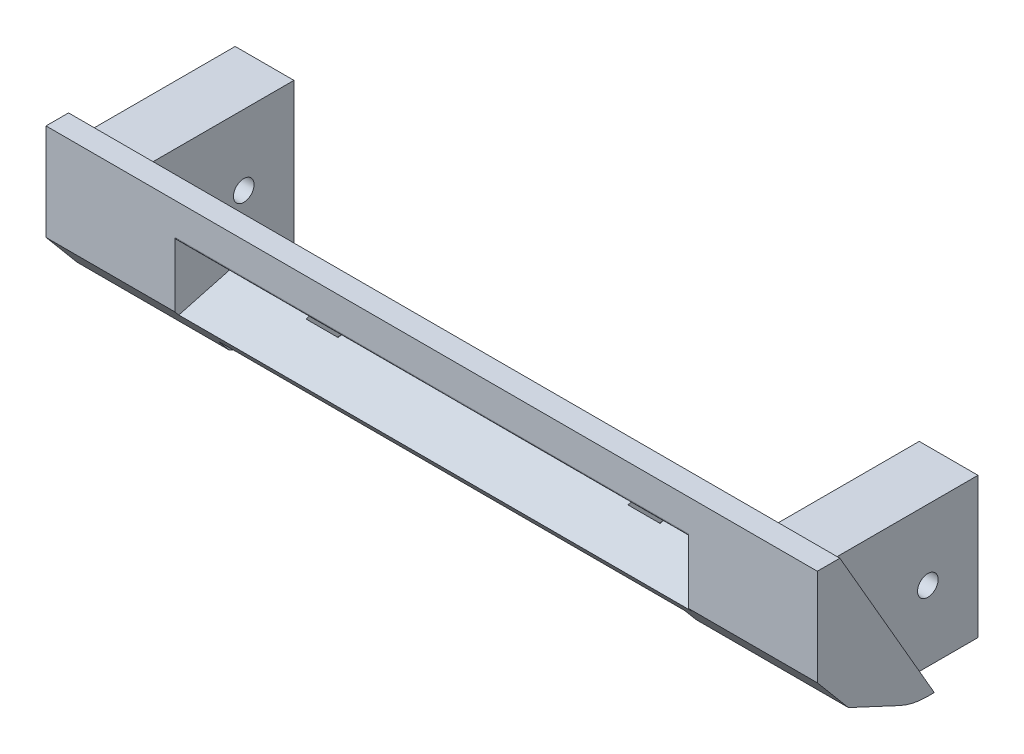
SolidWorks part; units mm, degrees
ref_plane "Front Plane" through (0, 0, 0) normal (0, 0, 1) x (1, 0, 0)
ref_plane "Top Plane" through (0, 0, 0) normal (0, 1, 0) x (1, 0, 0)
ref_plane "Right Plane" through (0, 0, 0) normal (1, 0, 0) x (0, 0, -1)
sketch "Sketch1" plane through (0, 0, 0) normal (1, 0, 0) x (0, 0, -1)
  line L0 (0, 0) -> (-29.3294, 50.8)
  line L1 (0, 0) -> (50, 0) construction
  line L2 (-29.3294, 50.8) -> (-36.3294, 50.8)
  line L3 (-36.3294, 13.8) -> (-6.7352, 0)
  line L6 (-36.3294, 50.8) -> (-36.3294, 13.8)
  line L7 (-6.7352, 0) -> (0, 0)
  line L8 (0, 0) -> (0, 21.8413) construction
  dimension "D1" = 65
  dimension "D2" = 6.7352
  dimension "D3" = 37
extrude "Boss-Extrude2" add sketch "Sketch1" along normal mid plane 239.55
sketch "Sketch2" plane through (0, 0, 0) normal (0, 0, 1) x (1, 0, 0)
  line L0 (0, 0) -> (0, 50.8) construction
  line L5 (115.75, 47.625) -> (96.7, 47.625) construction
  line L6 (115.75, 47.625) -> (115.75, 3.175) construction
  line L11 (115.75, 3.175) -> (96.7, 3.175) construction
  line L12 (96.7, 47.625) -> (96.7, 3.175) construction
  line L14 (115.35, 47.225) -> (115.35, 3.575)
  line L15 (115.35, 3.575) -> (97.1, 3.575)
  line L21 (119.775, 0) -> (-119.6, 0) construction
  line L28 (97.1, 47.225) -> (97.1, 3.575)
  line L29 (115.35, 47.225) -> (97.1, 47.225)
  line L30 (-96.7, 47.625) -> (-96.7, 3.175) construction
  line L31 (-115.75, 3.175) -> (-96.7, 3.175) construction
  line L32 (-115.75, 47.625) -> (-115.75, 3.175) construction
  line L33 (-115.75, 47.625) -> (-96.7, 47.625) construction
  line L34 (-115.35, 47.225) -> (-97.1, 47.225)
  line L35 (-97.1, 47.225) -> (-97.1, 3.575)
  line L36 (-115.35, 3.575) -> (-97.1, 3.575)
  line L37 (-115.35, 47.225) -> (-115.35, 3.575)
  line L40 (119.775, 50.8) -> (-119.775, 50.8) construction
  line L41 (119.775, 0) -> (119.775, 50.8) construction
  dimension "D2" = 19.05
  dimension "D4" = 3.175
  dimension "D7" = 4.025
  dimension "D1" = 193.4
  dimension "D3" = 3.175
  dimension "D5" = 0.4
extrude "Boss-Extrude1" add sketch "Sketch2" along normal up to surface and the other way blind 18 up to face at (0, 25.4, 14.6647)
sketch "Sketch12" plane through (0, -2.5797, 1.2029) normal (0, -0.9063, 0.4226) x (1, 0, 0)
  line L0 (-95.2, -603.0139) -> (-95.2, 0.9459) construction
  line L1 (-95.2, -603.0139) -> (-95.2, 0.9459) construction
  line L2 (119.775, 0) -> (-119.775, 0) construction
  line L3 (70, 15) -> (-70, 15)
  line L4 (70, 15) -> (70, 0)
  line L5 (70, 0) -> (-70, 0)
  line L6 (-70, 15) -> (-70, 0)
  line L7 (70, 15) -> (-70, 0) construction
  line L8 (70, 0) -> (-70, 15) construction
  line L10 (95.2, 44.3946) -> (-95.2, 44.3946)
  line L11 (95.2, 44.3946) -> (95.2, 19.3946)
  line L12 (95.2, 19.3946) -> (-95.2, 19.3946)
  line L13 (-95.2, 44.3946) -> (-95.2, 19.3946)
  line L14 (95.2, 44.3946) -> (-95.2, 19.3946) construction
  line L15 (95.2, 19.3946) -> (-95.2, 44.3946) construction
  line L16 (-120.6, 54.3946) -> (120.6, 54.3946) construction
  point P2 (0, 7.5)
  point P11 (0, 31.8946)
  dimension "D1" = 15
  dimension "D2" = 140
  dimension "D3" = 10
  dimension "D4" = 25
  dimension "D5" = 4.3946
extrude "Cut-Extrude4" [suppressed] cut sketch "Sketch12" against normal up to next
hole_wizard "M6 Clearance Hole1" positions "Sketch11" profile "Sketch10" hole size "M6" standard "ANSI Metric" end condition through all
sketch "Sketch11" plane through (115.35, 0, 0) normal (1, 0, 0) x (0, 0, -1)
  point P0 (2.4206, 25.4)
sketch "Sketch10" plane through (115.35, 25.4, -2.4206) normal (0, 1, 0) x (0, 0, -1)
  line L0 (0, 0) -> (0, 235.125)
  line L1 (0, 235.125) -> (3.2, 235.125)
  line L2 (3.2, 235.125) -> (3.2, 0)
  line L5 (3.2, 0) -> (0, 0)
  line L11 (0, -6.35) -> (0, 107.95) construction
  dimension "Thru Hole Dia." = 6.4
  dimension "Thru Hole Depth" = 235.125
sketch "Sketch13" plane through (0, 0, 0) normal (0, 0, 1) x (1, 0, 0)
  line L0 (119.775, 0) -> (-119.775, 0) construction
  line L1 (-72.5, 13.5) -> (72.5, 13.5)
  line L2 (-72.5, 13.5) -> (-72.5, 0)
  line L3 (-72.5, 0) -> (72.5, 0)
  line L4 (72.5, 13.5) -> (72.5, 0)
  line L5 (-72.5, 13.5) -> (72.5, 0) construction
  line L6 (-72.5, 0) -> (72.5, 13.5) construction
  line L7 (119.775, 50.8) -> (-119.775, 50.8) construction
  line L8 (-79.775, 23.8) -> (79.775, 23.8)
  line L9 (-79.775, 23.8) -> (-79.775, 37.8)
  line L10 (-79.775, 37.8) -> (79.775, 37.8)
  line L11 (79.775, 23.8) -> (79.775, 37.8)
  line L12 (-79.775, 23.8) -> (79.775, 37.8) construction
  line L13 (-79.775, 37.8) -> (79.775, 23.8) construction
  line L14 (-119.775, 50.8) -> (-119.775, 13.8) construction
  line L15 (0, 50.8) -> (0, -69.7748) construction
  point P0 (0, 6.75)
  point P7 (0, 30.8)
  dimension "D1" = 13.5
  dimension "D2" = 13
  dimension "D3" = 40
  dimension "D4" = 14
  dimension "D5" = 145
extrude "Cut-Extrude6" cut sketch "Sketch13" against normal through all both and the other way through all
chamfer "Chamfer5" distance 18 angle 15 1 edges at (0, 37.8, 21.8238) first distance on face at (0, 37.8, 29.0766)
chamfer "Chamfer6" distance 18 angle 15 1 edges at (0, 23.8, 36.3294) first distance on face at (0, 23.8, 25.0352)
chamfer "Chamfer7" distance 7 angle 40 1 edges at (0, 13.8, 36.3294) first distance on face at (0, 28.8566, 36.3294)
sketch "Sketch14" plane through (0, 13.5, 0) normal (0, -1, 0) x (1, 0, 0)
  line L0 (-50, 11.7942) -> (50, 11.7942) construction
  line L1 (72.5, 7.7942) -> (-72.5, 7.7942) construction
  line L2 (46.5, 15.7942) -> (53.5, 15.7942)
  line L3 (46.5, 15.7942) -> (46.5, 7.7942)
  line L4 (46.5, 7.7942) -> (53.5, 7.7942)
  line L5 (53.5, 15.7942) -> (53.5, 7.7942)
  line L6 (46.5, 15.7942) -> (53.5, 7.7942) construction
  line L7 (46.5, 7.7942) -> (53.5, 15.7942) construction
  line L9 (-53.5, 15.7942) -> (-46.5, 15.7942)
  line L10 (-53.5, 15.7942) -> (-53.5, 7.7942)
  line L11 (-53.5, 7.7942) -> (-46.5, 7.7942)
  line L12 (-46.5, 15.7942) -> (-46.5, 7.7942)
  line L13 (-53.5, 15.7942) -> (-46.5, 7.7942) construction
  line L14 (-53.5, 7.7942) -> (-46.5, 15.7942) construction
  point P0 (50, 11.7942)
  point P3 (0, 11.7942)
  point P10 (0, 0)
  dimension "D1" = 7
  dimension "D2" = 7
  dimension "D3" = 8
  dimension "D4" = 100
ref_plane "Plane2" through (0, 13.5, 7.7942) normal (0, 0.866, 0.5) x (-1, 0, 0)
sketch "Sketch15" plane through (0, 13.5, 7.7942) normal (0, 0.866, 0.5) x (-1, 0, 0)
  line L0 (-50, 3) -> (50, 3) construction
  line L1 (-72.5, 0) -> (72.5, 0) construction
  line L2 (-45, 6) -> (-55, 6)
  line L3 (-45, 6) -> (-45, 0)
  line L4 (-45, 0) -> (-55, 0)
  line L5 (-55, 6) -> (-55, 0)
  line L6 (-45, 6) -> (-55, 0) construction
  line L7 (-45, 0) -> (-55, 6) construction
  line L9 (45, 6) -> (55, 6)
  line L10 (45, 6) -> (45, 0)
  line L11 (45, 0) -> (55, 0)
  line L12 (55, 6) -> (55, 0)
  line L13 (45, 6) -> (55, 0) construction
  line L14 (45, 0) -> (55, 6) construction
  point P3 (0, 3)
  dimension "D1" = 10
  dimension "D2" = 10
  dimension "D3" = 6
  dimension "D4" = 100
extrude "Cut-Extrude8" cut sketch "Sketch15" along normal up to surface (14.7306 mm away) up to face at (0, 21.5558, 26.7049)
fillet "Fillet1" radius 4 1 edges at (0, 38.7363, 36.3294) second distance 1 first distance on face at (0, 40.3566, 30.2824)
fillet "Fillet2" radius 20 2 edges at (-96.1375, 0, 6.7352) (96.1375, 0, 6.7352)
equation "\"D1@Sketch2\"=187.05mm+0.25in"
equation "\"RailSpacing\"= 188.75mm"
equation "\"D1@Boss-Extrude2\"=\"RailSpacing\"+2in"
